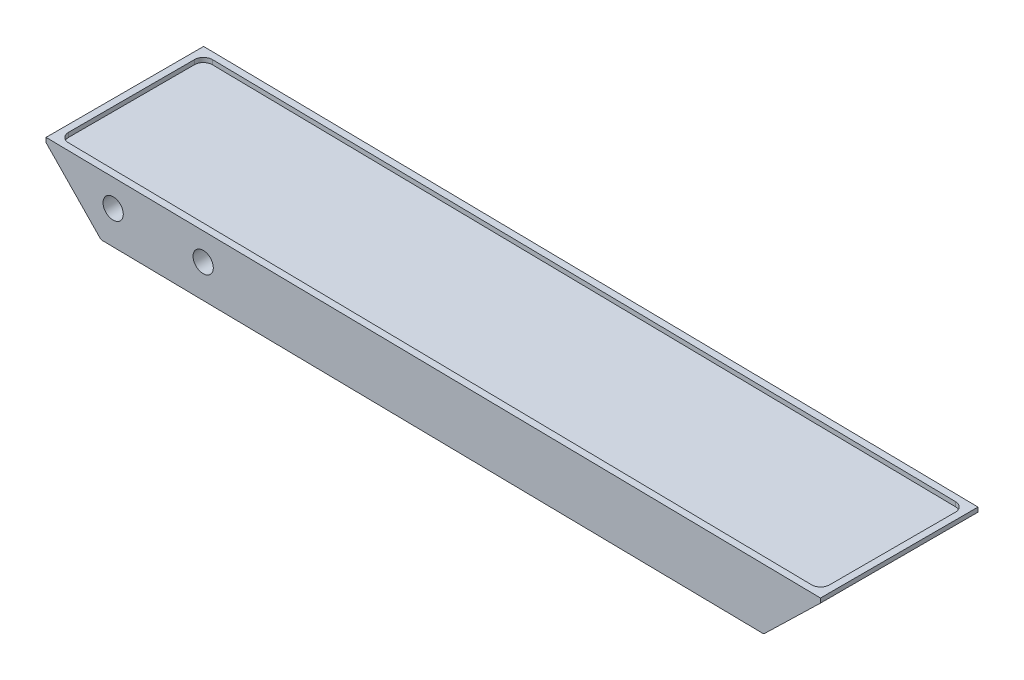
SolidWorks part; units mm, degrees
ref_plane "前视基准面" through (0, 0, 0) normal (0, 0, 1) x (1, 0, 0)
ref_plane "上视基准面" through (0, 0, 0) normal (0, 1, 0) x (1, 0, 0)
ref_plane "右视基准面" through (0, 0, 0) normal (1, 0, 0) x (0, 0, -1)
other "Configuration Table"
sketch "草图2" plane through (0, 0, 0) normal (0, 0, 1) x (1, 0, 0)
  line L0 (-128.5107, -0.6812) -> (-116.1374, 11.3224) construction
  line L1 (-116.1374, 11.3224) -> (-118.2263, 13.4756) construction
  line L2 (-118.2263, 13.4756) -> (-130.5996, 1.4721) construction
  line L3 (-131.1237, 1.2643) -> (-277.754, 3.4887) construction
  line L4 (-277.7995, 0.489) -> (-131.1692, -1.7354) construction
  line L5 (-278.2715, 3.7123) -> (-290.275, 16.0856) construction
  line L6 (-290.275, 16.0856) -> (-292.4283, 13.9967) construction
  line L7 (-292.4283, 13.9967) -> (-280.4247, 1.6234) construction
  line L8 (-128.5107, -0.6812) -> (-116.1374, 11.3224)
  line L9 (-116.1374, 11.3224) -> (-118.2263, 13.4756)
  line L10 (-118.2263, 13.4756) -> (-130.5996, 1.4721)
  line L11 (-131.1237, 1.2643) -> (-277.754, 3.4887)
  line L12 (-277.7995, 0.489) -> (-131.1692, -1.7354)
  line L13 (-278.2715, 3.7123) -> (-290.275, 16.0856)
  line L14 (-290.275, 16.0856) -> (-292.4283, 13.9967)
  line L15 (-292.4283, 13.9967) -> (-280.4247, 1.6234)
  line L16 (-290.275, 16.0856) -> (-118.2263, 13.4756)
  arc A0 (-131.1237, 1.2643) -> (-130.5996, 1.4721) centre (-131.1125, 2.0008) ccw construction
  arc A1 (-131.1692, -1.7354) -> (-128.5107, -0.6812) centre (-131.1125, 2.0008) ccw construction
  arc A2 (-278.2715, 3.7123) -> (-277.754, 3.4887) centre (-277.7428, 4.2252) ccw construction
  arc A3 (-280.4247, 1.6234) -> (-277.7995, 0.489) centre (-277.7428, 4.2252) ccw construction
  arc A4 (-131.1237, 1.2643) -> (-130.5996, 1.4721) centre (-131.1125, 2.0008) ccw
  arc A5 (-131.1692, -1.7354) -> (-128.5107, -0.6812) centre (-131.1125, 2.0008) ccw
  arc A6 (-278.2715, 3.7123) -> (-277.754, 3.4887) centre (-277.7428, 4.2252) ccw
  arc A7 (-280.4247, 1.6234) -> (-277.7995, 0.489) centre (-277.7428, 4.2252) ccw
  line M1 (-131.1237, 1.2643) -> (-277.754, 3.4887)
extrude "凸台-拉伸1" add sketch "草图2" against normal blind 35 contours L13 A6 A4 L10 L16 M1 region at (-204.3423, 8.7392, 0)
sketch "草图3" plane through (0.1772, 11.6794, 0) normal (0.0152, 0.9999, 0) x (0.9999, -0.0152, 0)
  line L0 (-119.9171, 1.5) -> (-119.9171, 33.5)
  line L1 (-119.9171, 33.5) -> (-288.9856, 33.5)
  line L2 (-288.9856, 33.5) -> (-288.9856, 1.5)
  line L3 (-288.9856, 1.5) -> (-119.9171, 1.5)
  line L4 (-290.4856, 0) -> (-118.4171, 0)
  line L5 (-118.4171, 0) -> (-118.4171, 35)
  line L6 (-118.4171, 35) -> (-290.4856, 35)
  line L7 (-290.4856, 35) -> (-290.4856, 0)
  line L8 (-290.4856, 0) -> (-118.4171, 0)
  line L9 (-118.4171, 0) -> (-118.4171, 35)
  line L10 (-118.4171, 35) -> (-290.4856, 35)
  line L11 (-290.4856, 35) -> (-290.4856, 0)
  dimension "D1" = 0
  dimension "D2" = 1.5
extrude "凸台-拉伸2" add sketch "草图3" along normal blind 1
fillet "圆角1" radius 2 4 edges at (-119.7185, 13.9983, -33.5) (-288.7676, 16.5628, -33.5) (-288.7676, 16.5628, -1.5) (-119.7185, 13.9983, -1.5)
sketch "草图4" plane through (0, 0, -35) normal (0, 0, -1) x (-1, 0, 0)
  line L0 (118.2111, 14.4755) -> (290.2598, 17.0855) construction
  line L1 (290.2598, 17.0855) -> (290.275, 16.0856) construction
  circle A0 centre (275.3526, 10.8587) radius 2.25
  circle A1 centre (255.3549, 10.5553) radius 2.25
  dimension "D1" = 4.5
  dimension "D3" = 19.9977
  dimension "D4" = 6
  dimension "D5" = 15
  dimension "D2" = 2
extrude "切除-拉伸1" cut sketch "草图4" against normal blind 6.55
sketch "草图5" plane through (0, 0, 0) normal (0, 0, 1) x (1, 0, 0)
  circle A0 centre (-255.3549, 10.5553) radius 2.25 construction
  circle A1 centre (-275.3526, 10.8587) radius 2.25 construction
  circle A2 centre (-255.3549, 10.5553) radius 2.25
  circle A3 centre (-275.3526, 10.8587) radius 2.25
extrude "切除-拉伸2" cut sketch "草图5" against normal blind 6.55
